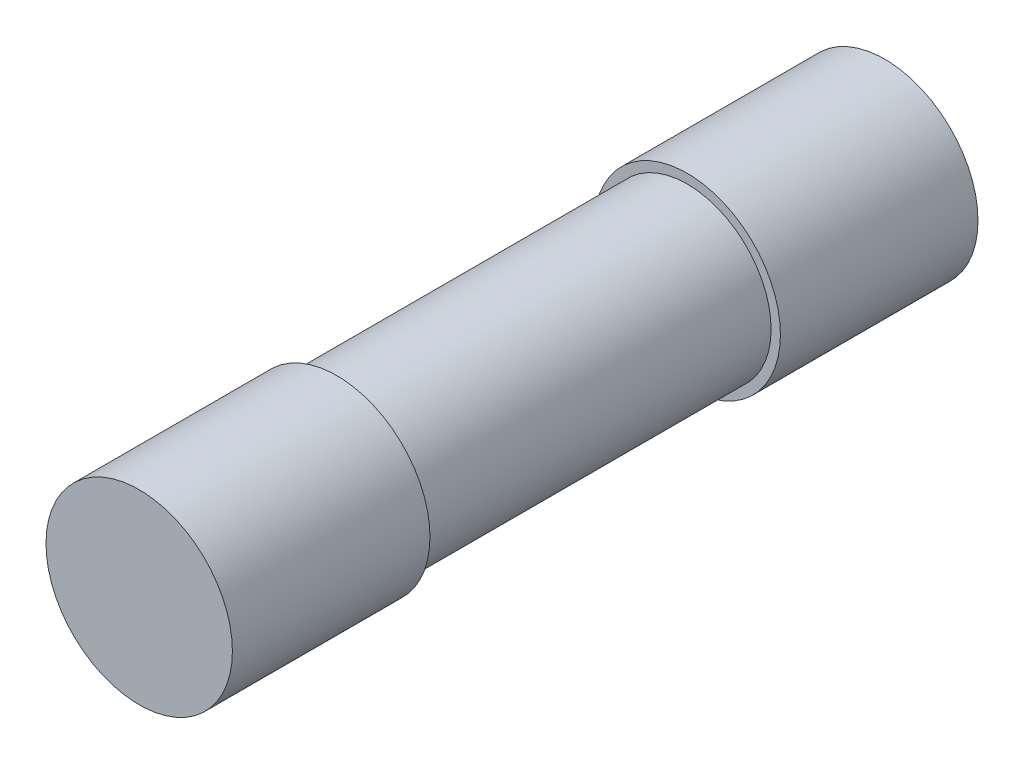
SolidWorks part; units mm, degrees
material "aluminio"
ref_plane "Alzado" through (0, 0, 0) normal (0, 0, 1) x (1, 0, 0)
ref_plane "Planta" through (0, 0, 0) normal (0, 1, 0) x (1, 0, 0)
ref_plane "Vista lateral" through (0, 0, 0) normal (1, 0, 0) x (0, 0, -1)
sketch "Sketch1" plane through (0, 0, 0) normal (0, 0, 1) x (1, 0, 0)
  circle A0 centre (0, 0) radius 2.25
  dimension "D1" = 4.5
extrude "Boss-Extrude1" add sketch "Sketch1" along normal blind 20
sketch "Sketch2" plane through (0, 0, 0) normal (0, 0, -1) x (-1, 0, 0)
  circle A0 centre (0, 0) radius 2.5
  dimension "D1" = 5
extrude "Boss-Extrude2" add sketch "Sketch2" against normal blind 5.3
extrude "Boss-Extrude3" add sketch "Sketch2<2>" against normal blind 5.3 from offset 14.7 offset against normal yes
sketch "Sketch2<2>" plane through (0, 0, 0) normal (0, 0, -1) x (-1, 0, 0) same geometry as "Sketch2"
